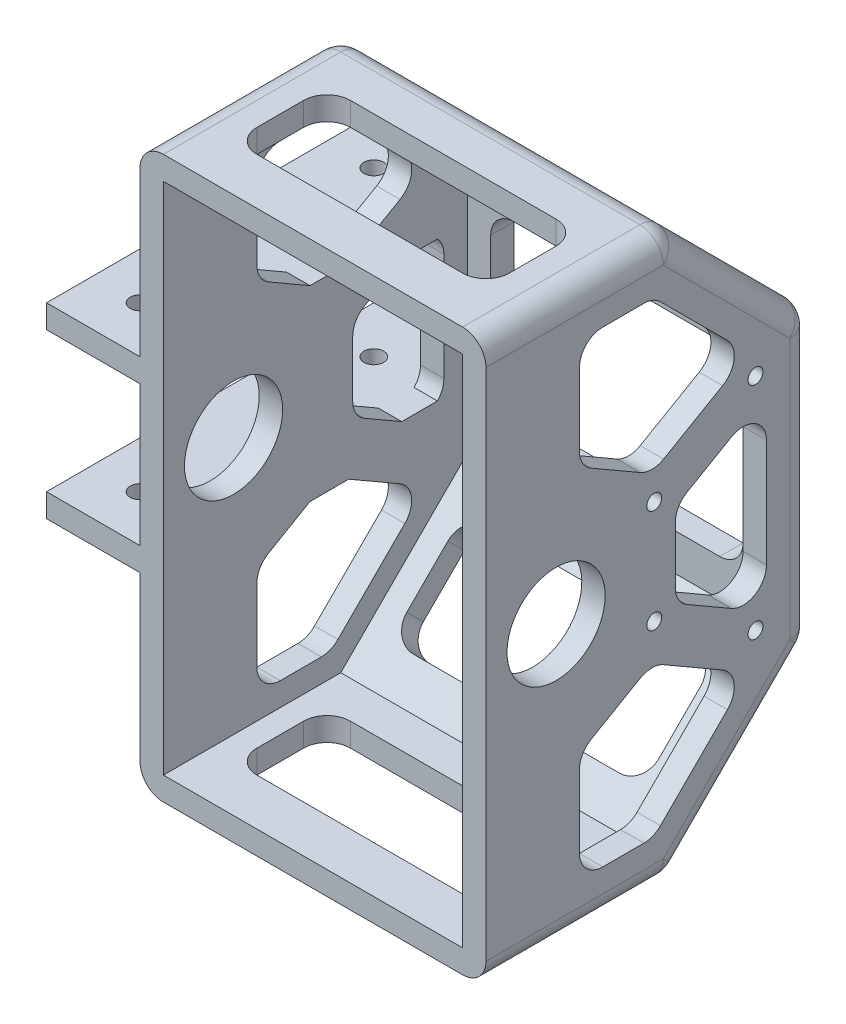
SolidWorks part; units mm, degrees
ref_plane "正面" through (0, 0, 0) normal (0, 0, 1) x (1, 0, 0)
ref_plane "平面" through (0, 0, 0) normal (0, 1, 0) x (1, 0, 0)
ref_plane "右側面" through (0, 0, 0) normal (1, 0, 0) x (0, 0, -1)
sketch "ｽｹｯﾁ1" plane through (0, 0, 0) normal (0, 0, 1) x (1, 0, 0)
  line L1 (-37, 60) -> (37, 60)
  line L2 (-37, 60) -> (-37, -60)
  line L3 (-37, -60) -> (37, -60)
  line L4 (37, 60) -> (37, -60)
  line L5 (-37, 60) -> (37, -60) construction
  line L6 (-37, -60) -> (37, 60) construction
  point P0 (0, 0)
  dimension "D1" = 120
  dimension "D2" = 74
extrude "ﾎﾞｽ - 押し出し1" add sketch "ｽｹｯﾁ1" along normal blind 70
chamfer "面取り2" distance 30 angle 45 2 edges at (0, 60, 0) (0, -60, 0)
sketch "ｽｹｯﾁ2" plane through (-37, 0, 0) normal (-1, 0, 0) x (0, 0, 1)
  line L0 (70, 60) -> (70, -60) construction
  line L1 (55, -23.6714) -> (55, -60)
  line L2 (55, 23.6714) -> (34.5, 11.8357)
  line L3 (34.5, 11.8357) -> (34.5, -11.8357)
  line L4 (34.5, -11.8357) -> (55, -23.6714)
  line L5 (55, -23.6714) -> (75.5, -11.8357)
  line L6 (75.5, -11.8357) -> (75.5, 11.8357)
  line L7 (75.5, 11.8357) -> (55, 23.6714)
  line L8 (70, -60) -> (30, -60) construction
  line L9 (34.5, -11.8357) -> (1.1122, -31.1122)
  line L10 (50, -23.6714) -> (50, -60)
  line L11 (0, -30) -> (30, -60) construction
  line L12 (55, 23.6714) -> (55, 60)
  line L13 (70, 60) -> (30, 60) construction
  line L14 (34.5, 11.8357) -> (1.1122, 31.1122)
  line L15 (30, 60) -> (0, 30) construction
  line L16 (32, -16.1658) -> (52.5, -28.0015)
  line L17 (32, -7.5056) -> (-1.3878, -26.782)
  line L18 (57.5, -28.0015) -> (80.5, -14.7224)
  line L19 (80.5, -14.7224) -> (80.5, 14.7224)
  line L20 (80.5, 14.7224) -> (57.5, 28.0015)
  line L21 (29.5, 11.8357) -> (29.5, -11.8357)
  line L22 (37, 16.1658) -> (3.6122, 35.4423)
  line L23 (52.5, 28.0015) -> (32, 16.1658)
  line L24 (60, 23.6714) -> (60, 60)
  line L25 (60, -23.6714) -> (60, -60)
  line L26 (37, -7.5056) -> (57.5, -19.3412)
  line L27 (37, -16.1658) -> (3.6122, -35.4423)
  line L28 (52.5, -19.3412) -> (70.5, -8.9489)
  line L29 (70.5, -8.9489) -> (70.5, 8.9489)
  line L30 (70.5, 8.9489) -> (52.5, 19.3412)
  line L31 (39.5, 11.8357) -> (39.5, -11.8357)
  line L32 (32, 7.5056) -> (-1.3878, 26.782)
  line L33 (57.5, 19.3412) -> (37, 7.5056)
  line L34 (50, 23.6714) -> (50, 60)
  line L47 (60, 50) -> (34.1421, 50)
  line L48 (34.1421, 50) -> (10, 25.8579)
  line L49 (10, 25.8579) -> (10, -25.8579)
  line L50 (10, -25.8579) -> (34.1421, -50)
  line L51 (34.1421, -50) -> (60, -50)
  line L52 (60, -50) -> (60, 50)
  line L53 (60, 50) -> (34.1421, 50)
  line L54 (34.1421, 50) -> (10, 25.8579)
  line L55 (10, 25.8579) -> (10, -25.8579)
  line L56 (10, -25.8579) -> (34.1421, -50)
  line L57 (34.1421, -50) -> (60, -50)
  line L58 (60, -50) -> (60, 50)
  circle A0 centre (55, 0) radius 10.5
  circle A1 centre (55, 0) radius 20.5 construction
  dimension "D1" = 21
  dimension "D2" = 15
  dimension "D3" = 41
  dimension "D4" = 5
  dimension "D5" = 5
  dimension "D6" = 10
shell "ｼｪﾙ1" thickness 5 removed face at (0, 0, 70)
extrude "ｶｯﾄ - 押し出し1" cut sketch "ｽｹｯﾁ2" against normal through all contours L56 L57 L10 L16 L27 | L32 L55 L17 L21 | L53 L54 L22 L23 L34 | L58 A0 | L58 A0 region at (-37, -34.4245, 35.5634) region at (-37, 0, 53.0853) region at (-37, 0, 62.2583) region at (-37, 34.4245, 35.5634) region at (-37, 0, 18.495)
sketch "ｽｹｯﾁ3" plane through (0, -15, -15) normal (0, -0.7071, -0.7071) x (1, 0, 0)
  line L8 (-27, 53.6396) -> (-27, 31.2132)
  line L9 (-27, 31.2132) -> (27, 31.2132)
  line L10 (27, 31.2132) -> (27, 53.6396)
  line L11 (27, 53.6396) -> (-27, 53.6396)
  line L12 (-27, 53.6396) -> (-27, 31.2132)
  line L13 (-27, 31.2132) -> (27, 31.2132)
  line L14 (27, 31.2132) -> (27, 53.6396)
  line L15 (27, 53.6396) -> (-27, 53.6396)
  dimension "D1" = 10
extrude "ｶｯﾄ - 押し出し2" cut sketch "ｽｹｯﾁ3" against normal blind 70
sketch "ｽｹｯﾁ4" plane through (0, 15, -15) normal (0, 0.7071, -0.7071) x (1, 0, 0)
  line L8 (27, -53.6396) -> (27, -31.2132)
  line L9 (27, -31.2132) -> (-27, -31.2132)
  line L10 (-27, -31.2132) -> (-27, -53.6396)
  line L11 (-27, -53.6396) -> (27, -53.6396)
  line L12 (27, -53.6396) -> (27, -31.2132)
  line L13 (27, -31.2132) -> (-27, -31.2132)
  line L14 (-27, -31.2132) -> (-27, -53.6396)
  line L15 (-27, -53.6396) -> (27, -53.6396)
  dimension "D1" = 10
extrude "ｶｯﾄ - 押し出し3" cut sketch "ｽｹｯﾁ4" against normal blind 70
sketch "ｽｹｯﾁ5" plane through (0, 0, 0) normal (0, 0, -1) x (-1, 0, 0)
  line L8 (27, -20) -> (27, 20)
  line L9 (27, 20) -> (-27, 20)
  line L10 (-27, 20) -> (-27, -20)
  line L11 (-27, -20) -> (27, -20)
  line L12 (27, -20) -> (27, 20)
  line L13 (27, 20) -> (-27, 20)
  line L14 (-27, 20) -> (-27, -20)
  line L15 (-27, -20) -> (27, -20)
  dimension "D1" = 10
extrude "ｶｯﾄ - 押し出し4" cut sketch "ｽｹｯﾁ5" against normal blind 70
sketch "ｽｹｯﾁ7" plane through (0, 60, 0) normal (0, 1, 0) x (1, 0, 0)
  line L8 (27, -60) -> (27, -40)
  line L9 (27, -40) -> (-27, -40)
  line L10 (-27, -40) -> (-27, -60)
  line L11 (-27, -60) -> (27, -60)
  line L12 (27, -60) -> (27, -40)
  line L13 (27, -40) -> (-27, -40)
  line L14 (-27, -40) -> (-27, -60)
  line L15 (-27, -60) -> (27, -60)
  dimension "D1" = 10
extrude "ｶｯﾄ - 押し出し5" cut sketch "ｽｹｯﾁ7" against normal through all
fillet "ﾌｨﾚｯﾄ1" radius 5 62 edges at (27, 51.1612, 24.6967) (-27, 51.1612, 24.6967) (-27, 35.3033, 8.8388) (27, 35.3033, 8.8388) (-27, 20, 2.5) (-27, -20, 2.5) (27, 20, 2.5) (27, -20, 2.5) (-27, -35.3033, 8.8388) (-27, -51.1612, 24.6967) (27, -51.1612, 24.6967) (27, -35.3033, 8.8388) (34.5, -50, 34.1421) (34.5, -29.596, 13.7382) (34.5, -17.6092, 34.5) (34.5, -26.5581, 50) (34.5, -50, 50) (34.5, 26.5581, 50) (34.5, 17.6092, 34.5) (34.5, 29.596, 13.7382) (34.5, 50, 34.1421) (34.5, 50, 50) (34.5, -20.2073, 10) (34.5, -8.9489, 29.5) (34.5, 8.9489, 29.5) (34.5, 20.2073, 10) (-34.5, 29.596, 13.7382) (-34.5, 50, 34.1421) (-34.5, 50, 50) (-34.5, 26.5581, 50) (-34.5, 17.6092, 34.5) (-34.5, 20.2073, 10) (-34.5, 8.9489, 29.5) (-34.5, -20.2073, 10) (-34.5, -8.9489, 29.5) (-34.5, -29.596, 13.7382) (-34.5, -17.6092, 34.5) (-34.5, -26.5581, 50) (-34.5, -50, 50) (-34.5, -50, 34.1421) (-27, -57.5, 60) (-27, -57.5, 40) (27, -57.5, 40) (27, -57.5, 60) (27, 57.5, 60) (27, 57.5, 40) (-27, 57.5, 40) (-27, 57.5, 60) (37, -45, 15) (37, -60, 50) (-37, -60, 50) (-37, -45, 15) (0, -30, 0) (-37, 0, 0) (-37, 45, 15) (0, 60, 30) (-37, 60, 50) (37, 60, 50) (0, 30, 0) (37, 45, 15) (37, 0, 0) (0, -60, 30)
sketch "ｽｹｯﾁ10" plane through (-37, 0, 0) normal (-1, 0, 0) x (0, 0, 1)
  line L0 (5, 27.9289) -> (5, -27.9289) construction
  line L1 (70, 17.5) -> (5, 17.5)
  line L2 (70, 17.5) -> (70, -17.5)
  line L3 (70, -17.5) -> (5, -17.5)
  line L4 (5, 17.5) -> (5, -17.5)
  line L5 (70, 17.5) -> (5, -17.5) construction
  line L6 (70, -17.5) -> (5, 17.5) construction
  line L7 (70, 55) -> (70, -55) construction
  line L8 (70, -15) -> (5, -15)
  line L9 (70, 20) -> (5, 20)
  line L10 (70, -20) -> (5, -20)
  line L11 (70, 15) -> (5, 15)
  line L13 (5, -15) -> (0, -15)
  line L14 (5, -15) -> (5, -20)
  line L15 (5, -20) -> (0, -20)
  line L16 (0, -15) -> (0, -20)
  line L17 (2.5, -20) -> (2.5, -15) construction
  line L18 (5, -17.5) -> (0, -17.5) construction
  line L19 (5, 20) -> (0, 20)
  line L20 (5, 20) -> (5, 15)
  line L21 (5, 15) -> (0, 15)
  line L22 (0, 20) -> (0, 15)
  line L23 (2.5, 15) -> (2.5, 20) construction
  line L24 (5, 17.5) -> (0, 17.5) construction
  circle A0 centre (55, 0) radius 10.5 construction
  point P0 (37.5, 0)
  point P110 (2.5, -17.5)
  point P114 (2.5, 17.5)
  line M12 (47.5, 25.1147) -> (37, 19.0526)
  arc M13 (37, 19.0526) -> (32, 19.0526) centre (34.5, 23.3827) cw
  line M14 (32, 19.0526) -> (19.3813, 26.338)
  arc M17 (10, 11.547) -> (17.5, 15.8771) centre (15, 11.547) cw
  line M18 (17.5, 15.8771) -> (27, 10.3923)
  line M22 (27, -10.3923) -> (17.5, -15.8771)
  arc M23 (17.5, -15.8771) -> (10, -11.547) centre (15, -11.547) cw
  line M28 (19.3813, -26.338) -> (32, -19.0526)
  arc M29 (32, -19.0526) -> (37, -19.0526) centre (34.5, -23.3827) cw
  line M30 (37, -19.0526) -> (47.5, -25.1147)
  line M36 (70, -55) -> (70, 55)
  line M39 (5, 27.9289) -> (5, -27.9289)
  dimension "D1" = 0
  dimension "D2" = 35
  dimension "D3" = 0
  dimension "D4" = 2.5
  dimension "D5" = 2.5
extrude "ﾎﾞｽ - 押し出し3" add sketch "ｽｹｯﾁ10" along normal blind 20 and the other way blind 5 contours L8 L4 L3 M36 M22 M23 | L10 L3 M36 M39 M28 M29 M30 | L11 L1 M36 M39 M17 M18 | L9 L1 M36 M12 M13 M14 M39 | L10 M30 M29 M28 | L9 M12 M14 M13 | L8 M22 M23 | L11 M18 M17 | L19 L22 L21 M39 | L13 L16 L15 L4 M39 region at (-37, 16.2819, 38.6398) region at (-37, 18.7162, 37.6667) region at (-37, 17.5, 2.5) region at (-37, -16.2819, 38.6398) region at (-37, 15.6213, 15.0573) region at (-37, 19.3583, 34.5) region at (-37, -17.5, 2.5) region at (-37, -18.7162, 37.6667) region at (-37, -15.6213, 15.0573) region at (-37, -19.3583, 34.5)
sketch "ｽｹｯﾁ12" plane through (0, -20, 0) normal (0, -1, 0) x (1, 0, 0)
  line L0 (-57, 70) -> (-57, 0) construction
  line L1 (-37, 70) -> (-57, 70) construction
  line L2 (-57, 70) -> (-57, 0) construction
  circle A0 centre (-47, 60) radius 2.1
  circle A1 centre (-47, 10) radius 2.1
  dimension "D1" = 10
  dimension "D2" = 10
  dimension "D3" = 4.2
  dimension "D4" = 50
  dimension "D5" = 4.2
  dimension "D6" = 10
extrude "ｶｯﾄ - 押し出し7" cut sketch "ｽｹｯﾁ12" against normal through all
sketch "ｽｹｯﾁ13" plane through (37, 0, 0) normal (1, 0, 0) x (0, 0, -1)
  circle A0 centre (-12.3494, 24.6244) radius 1.6
  circle A1 centre (-34, 12.1244) radius 1.6
  circle A2 centre (-34, -10.0111) radius 1.6
  circle A3 centre (-12.3494, -22.5111) radius 1.6
extrude "ｶｯﾄ - 押し出し8" cut sketch "ｽｹｯﾁ13" against normal blind 10
